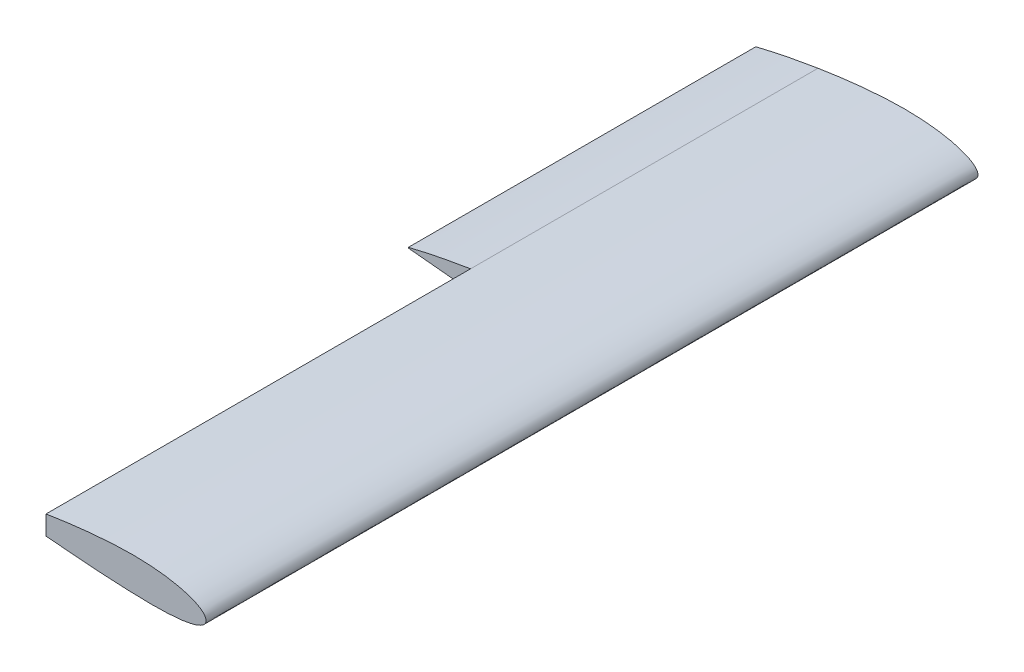
SolidWorks part; units mm, degrees
ref_plane "Front Plane" through (0, 0, 0) normal (0, 0, 1) x (1, 0, 0)
ref_plane "Top Plane" through (0, 0, 0) normal (0, 1, 0) x (1, 0, 0)
ref_plane "Right Plane" through (0, 0, 0) normal (1, 0, 0) x (0, 0, -1)
sketch "Sketch1" plane through (0, 0, 0) normal (0, 0, 1) x (1, 0, 0)
  line L0 (-232.0798, 18.6403) -> (-232.0798, -9.2995)
  spline S0 degree 3 poles (-232.0798, 18.6403) (-229.1643, 19.1051) (-222.2911, 20.2009) (-211.3375, 21.8003) (-199.1467, 23.4589) (-186.7095, 24.9978) (-174.1041, 26.3964) (-161.4086, 27.6282) (-148.7028, 28.67) (-136.0486, 29.4987) (-123.5023, 30.1004) (-111.1413, 30.381) (-99.0664, 30.3378) (-87.3818, 29.9639) (-76.166, 29.2625) (-65.4942, 28.2421) (-55.4376, 26.9176) (-46.0625, 25.3096) (-37.4298, 23.4441) (-29.5941, 21.3513) (-22.603, 19.0647) (-16.4967, 16.6189) (-11.3071, 14.0482) (-7.0567, 11.3833) (-3.7587, 8.6453) (-1.4211, 5.8377) (-0.0765, 2.934) (0.1754, -0.0176) (-0.6552, -2.8586) (-2.5307, -5.4396) (-5.3368, -7.7439) (-9.0399, -9.8146) (-13.6249, -11.6648) (-19.0703, -13.295) (-25.3465, -14.701) (-32.4168, -15.8791) (-40.2393, -16.8276) (-48.7681, -17.5483) (-57.9533, -18.0468) (-67.7426, -18.3331) (-78.0803, -18.4209) (-88.9087, -18.3281) (-100.1673, -18.0756) (-111.7935, -17.6875) (-123.7453, -17.1857) (-135.9735, -16.6041) (-148.4028, -15.8904) (-160.9356, -15.0745) (-173.4784, -14.1779) (-185.9552, -13.2219) (-198.2901, -12.2258) (-210.4075, -11.2062) (-221.6469, -10.2324) (-228.8379, -9.5894) (-232.0798, -9.2995) knots 0 0 0 0 0.018424 0.043434 0.06908 0.095203 0.12164 0.148227 0.1748 0.201195 0.227364 0.253182 0.278347 0.30271 0.326128 0.348467 0.3696 0.389416 0.407811 0.424699 0.440008 0.453688 0.465715 0.476104 0.484928 0.49236 0.49873 0.504587 0.510443 0.516804 0.524199 0.532941 0.543186 0.554996 0.568376 0.583299 0.599709 0.617539 0.636704 0.657109 0.678651 0.701217 0.724685 0.748928 0.773811 0.799338 0.825326 0.851504 0.877716 0.9038 0.929596 0.954944 0.979688 1 1 1 1
extrude "Boss-Extrude1" add sketch "Sketch1" along normal blind 1120
sketch "Sketch2" plane through (0, 0, 0) normal (0, 0, 1) x (1, 0, 0)
  line L0 (-232.0798, 18.6403) -> (-232.0798, -9.2995)
  line L1 (-322.333, 0.5148) -> (-322.333, -0.5066)
  spline S0 degree 3 poles (-232.0798, 18.6403) (-232.9971, 18.4966) (-237.5995, 17.7757) (-245.6979, 16.3987) (-256.1817, 14.5496) (-266.0705, 12.7084) (-275.3065, 10.9119) (-283.8343, 9.1839) (-291.6033, 7.5511) (-298.5679, 6.0388) (-304.6872, 4.6711) (-309.9259, 3.4706) (-314.2535, 2.4578) (-317.6452, 1.6505) (-320.0818, 1.0631) (-321.538, 0.709) (-322.1805, 0.552) (-322.333, 0.5148) knots 0 0 0 0 0.030252 0.151774 0.267626 0.37709 0.479485 0.574175 0.66057 0.73813 0.806369 0.864859 0.913229 0.951173 0.978451 0.994887 1 1 1 1
  spline S1 degree 3 poles (-232.0798, -9.2995) (-232.6657, -9.2475) (-236.9346, -8.868) (-244.7159, -8.1558) (-255.2335, -7.1827) (-265.179, -6.2448) (-274.4894, -5.353) (-283.1057, -4.5145) (-290.9725, -3.7372) (-298.0392, -3.0286) (-304.2602, -2.3953) (-309.5949, -1.8468) (-314.0082, -1.3828) (-317.4721, -1.0277) (-319.9612, -0.741) (-321.4641, -0.6201) (-322.142, -0.5059) (-322.3217, -0.5065) (-322.333, -0.5066) knots 0 0 0 0 0.019463 0.141781 0.258505 0.3689 0.472262 0.567931 0.655294 0.733785 0.802892 0.862162 0.911205 0.949694 0.977373 0.994054 0.999628 1 1 1 1
extrude "Boss-Extrude2" add sketch "Sketch2" along normal blind 504
sketch "Sketch3" plane through (0, 0, 0) normal (0, 0, 1) x (1, 0, 0)
  circle A0 centre (-96.7, 6.044) radius 12.7
extrude "Cut-Extrude1" cut sketch "Sketch3" along normal blind 801
ref_plane "Plane1" through (0, 0, 330.7) normal (0, 0, 1) x (1, 0, 0)
sketch "Sketch4" plane through (0, 0, 330.7) normal (0, 0, 1) x (1, 0, 0)
  line L0 (-112.7, -19.138) -> (-80.7, -19.138)
  line L1 (-80.7, -19.138) -> (-80.7, 21.744)
  line L2 (-80.7, 21.744) -> (-112.7, 21.744)
  line L3 (-112.7, 21.744) -> (-112.7, -19.138)
extrude "Cut-Extrude2" cut sketch "Sketch4" along normal blind 46
ref_plane "Plane2" through (0, 0, 330.7) normal (0, 0, 1) x (1, 0, 0)
sketch "Sketch5" plane through (0, 0, 330.7) normal (0, 0, 1) x (1, 0, 0)
  line L0 (-287.8664, -8.987) -> (-227.8664, -8.987)
  line L1 (-227.8664, -8.987) -> (-227.8664, 3.013)
  line L2 (-227.8664, 3.013) -> (-287.8664, 3.013)
  line L3 (-287.8664, 3.013) -> (-287.8664, -8.987)
extrude "Cut-Extrude3" cut sketch "Sketch5" along normal blind 46
ref_plane "Plane3" through (0, 0, 534.5) normal (0, 0, 1) x (1, 0, 0)
sketch "Sketch6" plane through (0, 0, 534.5) normal (0, 0, 1) x (1, 0, 0)
  line L0 (-204.283, -16.91) -> (-150.283, -16.91)
  line L1 (-150.283, -16.91) -> (-150.283, 12.19)
  line L2 (-150.283, 12.19) -> (-204.283, 12.19)
  line L3 (-204.283, 12.19) -> (-204.283, -16.91)
extrude "Cut-Extrude4" cut sketch "Sketch6" along normal blind 64
ref_plane "Plane4" through (0, 0, -0.5) normal (0, 0, 1) x (1, 0, 0)
sketch "Sketch7" plane through (0, 0, -0.5) normal (0, 0, 1) x (1, 0, 0)
  line L0 (-235.833, 1.435) -> (-215.433, 1.435)
  line L1 (-215.433, 1.435) -> (-215.433, 8.235)
  line L2 (-215.433, 8.235) -> (-235.833, 8.235)
  line L3 (-235.833, 8.235) -> (-235.833, 1.435)
extrude "Cut-Extrude5" cut sketch "Sketch7" along normal blind 26
